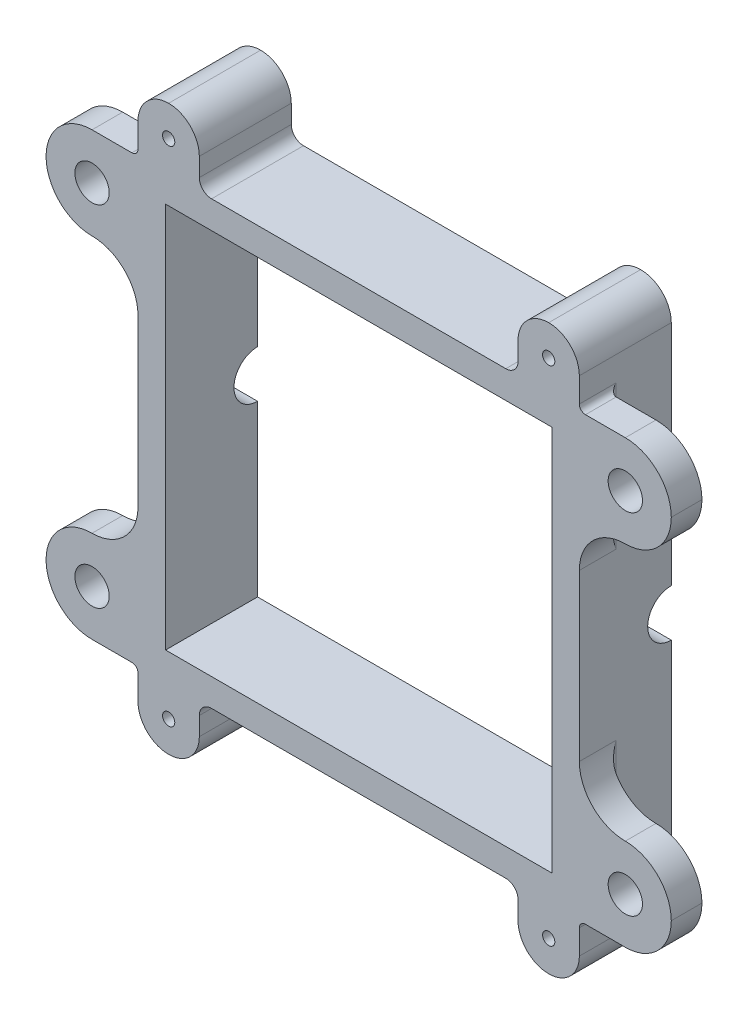
SolidWorks part; units mm, degrees
ref_plane "Front Plane" through (0, 0, 0) normal (0, 0, 1) x (1, 0, 0)
ref_plane "Top Plane" through (0, 0, 0) normal (0, 1, 0) x (1, 0, 0)
ref_plane "Right Plane" through (0, 0, 0) normal (1, 0, 0) x (0, 0, -1)
sketch "Sketch1" plane through (0, 0, 0) normal (0, 0, 1) x (1, 0, 0)
  line L1 (-45.72, -45.72) -> (45.72, -45.72)
  line L2 (-45.72, -45.72) -> (-45.72, 45.72)
  line L3 (-45.72, 45.72) -> (45.72, 45.72)
  line L4 (45.72, -45.72) -> (45.72, 45.72)
  line L5 (-45.72, -45.72) -> (45.72, 45.72) construction
  line L6 (-45.72, 45.72) -> (45.72, -45.72) construction
  point P0 (0, 0)
  dimension "D1" = 91.44
  dimension "D2" = 91.44
extrude "Boss-Extrude1" add sketch "Sketch1" along normal blind 19.05
sketch "Sketch2" plane through (0, 0, 19.05) normal (0, 0, 1) x (1, 0, 0)
  line L1 (-40.005, -40.005) -> (40.005, -40.005)
  line L2 (-40.005, -40.005) -> (-40.005, 40.005)
  line L3 (-40.005, 40.005) -> (40.005, 40.005)
  line L4 (40.005, -40.005) -> (40.005, 40.005)
  line L5 (-40.005, -40.005) -> (40.005, 40.005) construction
  line L6 (-40.005, 40.005) -> (40.005, -40.005) construction
  point P0 (0, 0)
  dimension "D1" = 80.01
  dimension "D2" = 80.01
extrude "Cut-Extrude1" cut sketch "Sketch2" against normal through all
sketch "Sketch3" plane through (45.72, 0, 0) normal (1, 0, 0) x (0, 0, -1)
  line L0 (0, -45.72) -> (0, 45.72) construction
  circle A0 centre (0, 0) radius 4.8895
  circle A1 centre (0, 57.404) radius 4.8895
  circle A2 centre (0, -57.404) radius 4.8895
  dimension "D1" = 9.779
  dimension "D2" = 9.779
  dimension "D3" = 9.779
  dimension "D4" = 57.404
  dimension "D5" = 57.404
extrude "Cut-Extrude2" cut sketch "Sketch3" against normal through all
sketch "Sketch4" plane through (0, 0, 0) normal (0, 0, -1) x (-1, 0, 0)
  line L1 (-45.72, 45.72) -> (-33.02, 45.72)
  line L2 (-45.72, 45.72) -> (-45.72, 58.42)
  line L3 (-45.72, 58.42) -> (-33.02, 58.42)
  line L4 (-33.02, 45.72) -> (-33.02, 58.42)
  dimension "D1" = 12.7
  dimension "D2" = 12.7
extrude "Boss-Extrude2" add sketch "Sketch4" against normal through all
sketch "Sketch5" plane through (0, 0, 19.05) normal (0, 0, 1) x (1, 0, 0)
  line L0 (33.02, 52.07) -> (45.72, 52.07) construction
  line L3 (39.37, 58.42) -> (39.37, 45.72) construction
  line L6 (45.72, 58.42) -> (45.72, -45.72) construction
  line L7 (33.02, 58.42) -> (45.72, 58.42) construction
  circle A0 centre (39.37, 52.07) radius 1.27
  dimension "D4" = 2.54
  dimension "D1" = 6.35
  dimension "D2" = 6.35
  dimension "D3" = 6.35
extrude "Cut-Extrude3" cut sketch "Sketch5" against normal through all
fillet "Fillet1" radius 6.35 2 edges at (33.02, 58.42, 9.525) (45.72, 58.42, 9.525)
sketch "Sketch6" plane through (0, 0, 0) normal (0, 0, -1) x (-1, 0, 0)
  line L1 (-45.72, -45.72) -> (-33.02, -45.72)
  line L2 (-45.72, -45.72) -> (-45.72, -58.42)
  line L3 (-45.72, -58.42) -> (-33.02, -58.42)
  line L4 (-33.02, -45.72) -> (-33.02, -58.42)
  circle A0 centre (-39.37, -52.07) radius 1.27
  dimension "D5" = 2.54
  dimension "D1" = 12.7
  dimension "D2" = 12.7
  dimension "D3" = 6.35
  dimension "D4" = 6.35
extrude "Boss-Extrude3" add sketch "Sketch6" against normal through all
fillet "Fillet4" radius 6.35 2 edges at (45.72, -58.42, 9.525) (33.02, -58.42, 9.525)
mirror "Mirror8" about plane through (0, 0, 0) normal (1, 0, 0) of "Fillet4", "Boss-Extrude3", "Fillet1", "Cut-Extrude3", "Boss-Extrude2"
fillet "Fillet5" radius 2.54 4 edges at (33.02, -45.72, 9.525) (-33.02, -45.72, 9.525) (33.02, 45.72, 9.525) (-33.02, 45.72, 9.525)
sketch "Sketch7" plane through (0, 0, 19.05) normal (0, 0, 1) x (1, 0, 0)
  line L0 (3.6422, 45.72) -> (58.2632, 45.72) construction
  line L2 (40.005, 40.005) -> (-40.005, 40.005) construction
  line L3 (-45.72, 52.07) -> (-45.72, -52.07) construction
  line L4 (-45.72, 45.72) -> (-64.77, 45.72)
  line L5 (-45.72, 45.72) -> (-45.72, 26.67)
  line L6 (-45.72, 26.67) -> (-64.77, 26.67)
  line L7 (-64.77, 45.72) -> (-64.77, 26.67)
  line L8 (-40.005, 0) -> (40.005, 0) construction
  line L9 (-40.005, 40.005) -> (-40.005, -40.005) construction
  line L10 (40.005, -40.005) -> (40.005, 40.005) construction
  line L11 (0, 40.005) -> (0, -40.005) construction
  line L12 (-40.005, -40.005) -> (40.005, -40.005) construction
  line L13 (-45.72, -45.72) -> (-64.77, -45.72)
  line L14 (-64.77, -45.72) -> (-64.77, -26.67)
  line L15 (-45.72, -26.67) -> (-64.77, -26.67)
  line L16 (-45.72, -26.67) -> (-45.72, -45.72)
  line L17 (45.72, 45.72) -> (64.77, 45.72)
  line L18 (64.77, 45.72) -> (64.77, 26.67)
  line L19 (45.72, 26.67) -> (64.77, 26.67)
  line L20 (45.72, 45.72) -> (45.72, 26.67)
  line L21 (45.72, -26.67) -> (45.72, -45.72)
  line L22 (45.72, -26.67) -> (64.77, -26.67)
  line L23 (64.77, -45.72) -> (64.77, -26.67)
  line L24 (45.72, -45.72) -> (64.77, -45.72)
  line L25 (30.48, 45.72) -> (-30.48, 45.72) construction
  circle A0 centre (-55.245, 36.195) radius 3.556
  circle A1 centre (-55.245, -36.195) radius 3.556
  circle A2 centre (55.245, 36.195) radius 3.556
  circle A3 centre (55.245, -36.195) radius 3.556
  dimension "D4" = 7.112
  dimension "D2" = 19.05
  dimension "D3" = 19.05
  dimension "D5" = 9.525
  dimension "D6" = 9.525
extrude "Boss-Extrude4" add sketch "Sketch7" against normal blind 6.35
fillet "Fillet6" radius 9.525 12 edges at (64.77, -45.72, 15.875) (45.72, -26.67, 15.875) (64.77, -26.67, 15.875) (45.72, 26.67, 15.875) (64.77, 26.67, 15.875) (64.77, 45.72, 15.875) (-45.72, 26.67, 15.875) (-64.77, 45.72, 15.875) (-64.77, 26.67, 15.875) (-45.72, -26.67, 15.875) (-64.77, -45.72, 15.875) (-64.77, -26.67, 15.875)
fillet "Fillet7" radius 1.27 4 edges at (-45.72, -31.4325, 12.7) (-45.72, 31.4325, 12.7) (45.72, -31.4325, 12.7) (45.72, 31.4325, 12.7)
fillet "Fillet8" radius 1.27 4 edges at (-45.72, 45.72, 15.24) (-45.72, -45.72, 15.24) (45.72, -45.72, 15.24) (45.72, 45.72, 15.24)
